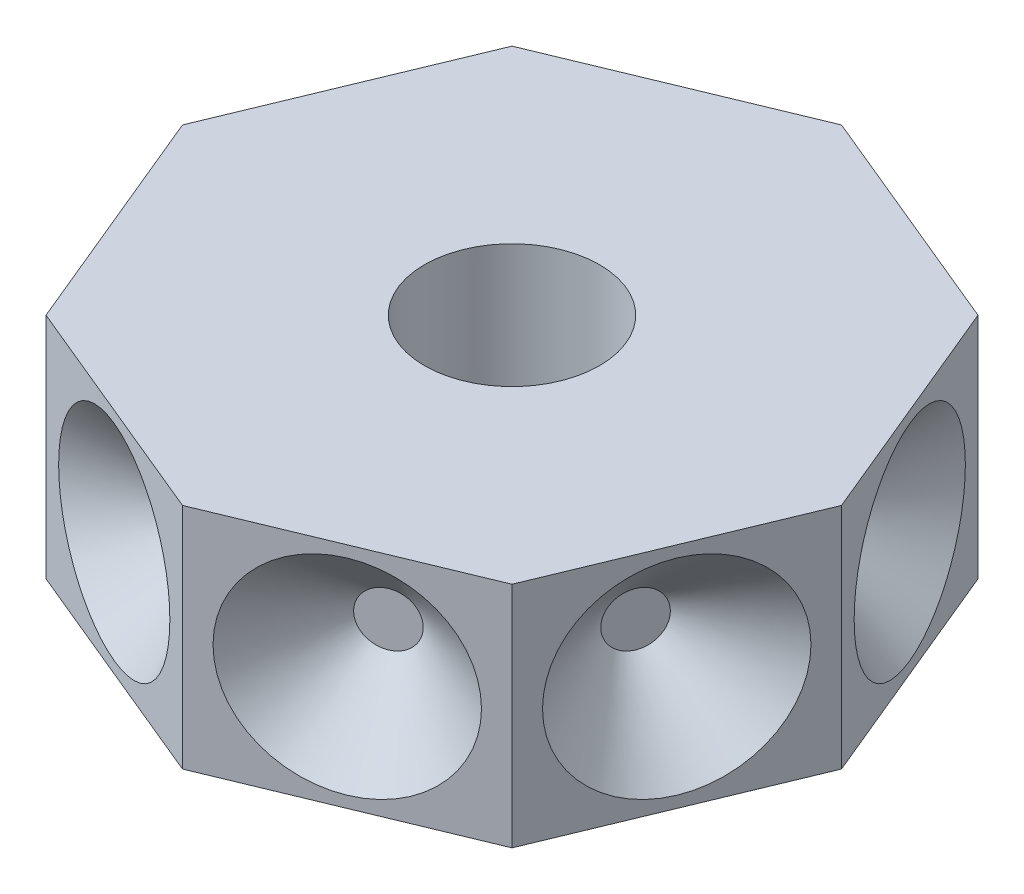
SolidWorks part; units mm, degrees
ref_plane "Front Plane" through (0, 0, 0) normal (0, 0, 1) x (1, 0, 0)
ref_plane "Top Plane" through (0, 0, 0) normal (0, 1, 0) x (1, 0, 0)
ref_plane "Right Plane" through (0, 0, 0) normal (1, 0, 0) x (0, 0, -1)
sketch "Sketch1" plane through (0, 0, 0) normal (0, 1, 0) x (1, 0, 0)
  line L0 (4.3296, 0) -> (3.0615, 3.0615)
  line L1 (0, 4.3296) -> (-3.0615, 3.0615)
  line L2 (-3.0615, 3.0615) -> (-4.3296, 0)
  line L3 (-4.3296, 0) -> (-3.0615, -3.0615)
  line L4 (-3.0615, -3.0615) -> (0, -4.3296)
  line L5 (0, -4.3296) -> (3.0615, -3.0615)
  line L6 (3.0615, -3.0615) -> (4.3296, 0)
  line L7 (3.0615, 3.0615) -> (0, 4.3296)
  circle A0 centre (0, 0) radius 4.5 construction
  circle A1 centre (0, 0) radius 4 construction
  dimension "D1" = 9
  dimension "D2" = 8
extrude "Boss-Extrude1" add sketch "Sketch1" along normal blind 3
sketch "Sketch2" plane through (0, 0, 0) normal (0, -1, 0) x (1, 0, 0)
  circle A0 centre (0, 0) radius 1.15
  dimension "D1" = 2.3
extrude "Cut-Extrude1" cut sketch "Sketch2" against normal up to surface (3 mm away) up to face at (0, 3, 0)
ref_axis "Axis1" through (0, -0.15, 0) along (0, 1, 0)
sketch "Sketch3" plane through (-1.5307, 0, 3.6955) normal (-0.3827, 0, 0.9239) x (0.9239, 0, 0.3827)
  line L1 (-1.6569, 0) -> (1.6569, 3) construction
  line L2 (-1.6569, 3) -> (1.6569, 0) construction
  circle A0 centre (0, 1.5) radius 0.15
  dimension "D1" = 0.3
extrude "Cut-Extrude2" cut sketch "Sketch3" against normal blind 1 contours A0
chamfer "Chamfer1" distance 1.2 angle 45 1 edges at (-1.3922, 1.5, 3.7529)
pattern_circular "CirPattern3" count 8 over 360 about axis through (0, -0.15, 0) along (0, 1, 0) of "Cut-Extrude2"
chamfer "Chamfer2" distance 1.2 angle 45 7 edges at (1.6693, 1.5, 3.6381) (3.7529, 1.5, 1.3922) (-3.6381, 1.5, 1.6693) (-3.7529, 1.5, -1.3922) (-1.6693, 1.5, -3.6381) (1.3922, 1.5, -3.7529) (3.6381, 1.5, -1.6693)
